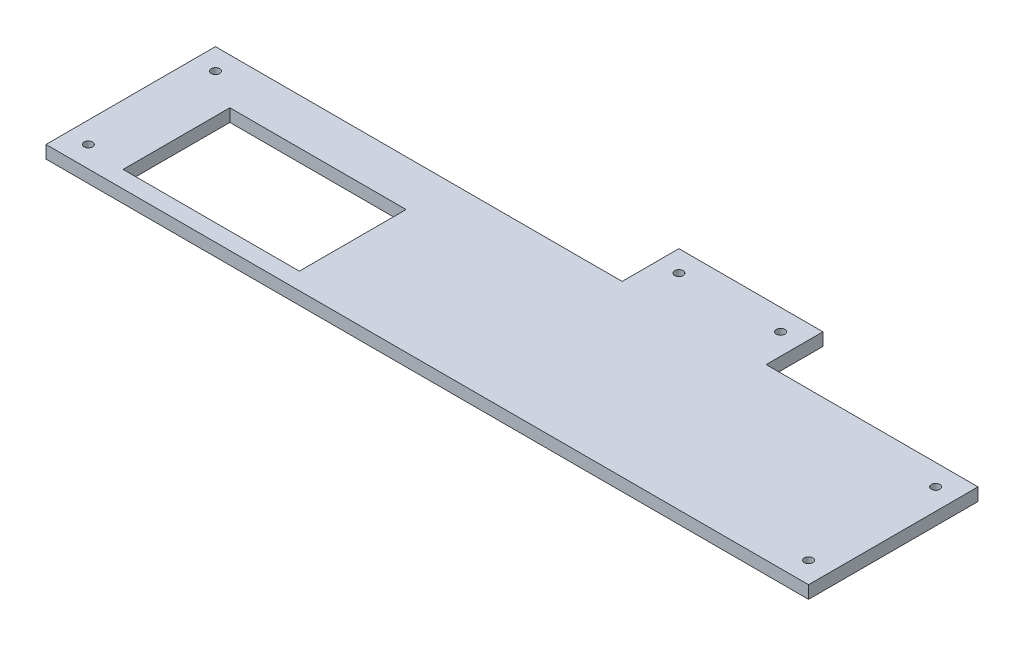
SolidWorks part; units mm, degrees
ref_plane "Front Plane" through (0, 0, 0) normal (0, 0, 1) x (1, 0, 0)
ref_plane "Top Plane" through (0, 0, 0) normal (0, 1, 0) x (1, 0, 0)
ref_plane "Right Plane" through (0, 0, 0) normal (1, 0, 0) x (0, 0, -1)
sketch "Sketch1" plane through (0, 0, 0) normal (0, 1, 0) x (1, 0, 0)
  line L8 (450, 100) -> (-450, 100)
  line L9 (-450, 100) -> (-450, -100)
  line L10 (-450, -100) -> (450, -100)
  line L11 (450, -100) -> (450, 100)
  circle A4 centre (425, -75) radius 5
  circle A5 centre (425, 75) radius 5
  circle A6 centre (-425, -75) radius 5
  circle A7 centre (-425, 75) radius 5
extrude "Boss-Extrude1" add sketch "Sketch1" against normal blind 15
sketch "Sketch2" plane through (0, -15, 0) normal (0, -1, 0) x (1, 0, 0)
  line L1 (-379, 80) -> (-171, 80)
  line L2 (-379, 80) -> (-379, -46)
  line L3 (-379, -46) -> (-171, -46)
  line L4 (-171, 80) -> (-171, -46)
extrude "Shredder Opening" cut sketch "Sketch2" against normal through all
sketch "Sketch3" plane through (0, 0, 0) normal (0, 1, 0) x (1, 0, 0)
  line L0 (450, 100) -> (-450, 100) construction
  line L1 (200, 100) -> (30, 100)
  line L2 (200, 100) -> (200, 167)
  line L3 (200, 167) -> (30, 167)
  line L4 (30, 100) -> (30, 167)
  line L5 (180, -91) -> (180, 147) construction
  line L6 (50, 147) -> (180, 147) construction
  line L7 (50, -91) -> (50, 147) construction
  line L8 (115, 167) -> (115, 267.7218) construction
  circle A0 centre (175, 142) radius 5 construction
  circle A1 centre (175, 142) radius 5
  circle A2 centre (55, 142) radius 5
  dimension "D1" = 20
  dimension "D2" = 20
  dimension "D3" = 20
extrude "Legs add on" add sketch "Sketch3" against normal through all
